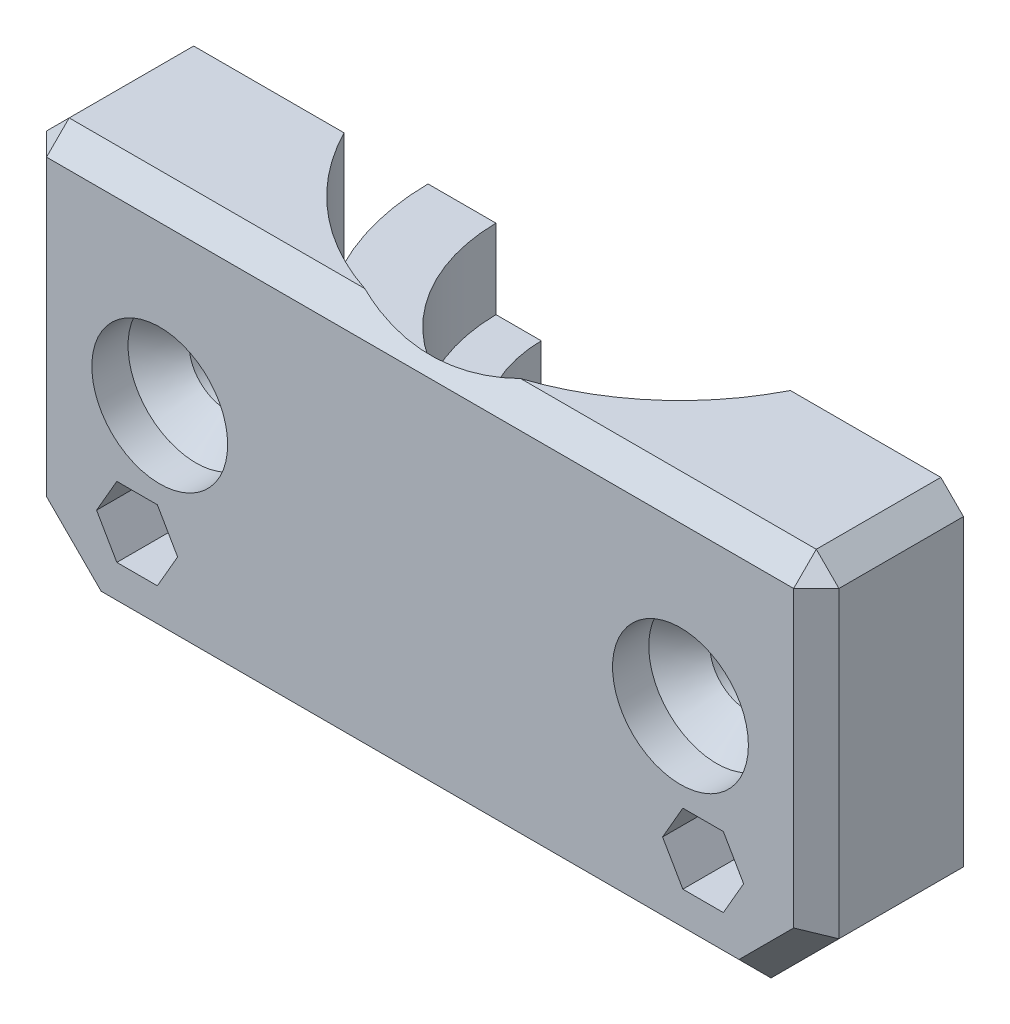
SolidWorks part; units mm, degrees
ref_plane "Front Plane" through (0, 0, 0) normal (0, 0, 1) x (1, 0, 0)
ref_plane "Top Plane" through (0, 0, 0) normal (0, 1, 0) x (1, 0, 0)
ref_plane "Right Plane" through (0, 0, 0) normal (1, 0, 0) x (0, 0, -1)
sketch "Sketch1" plane through (0, 0, 0) normal (0, 1, 0) x (1, 0, 0)
  circle A0 centre (0, 0) radius 8.05
  circle A1 centre (0, 0) radius 11.05
  dimension "D1" = 16.1
  dimension "D2" = 3
extrude "Boss-Extrude1" add sketch "Sketch1" along normal blind 3.5
sketch "Sketch2" plane through (0, 0, 0) normal (0, -1, 0) x (-1, 0, 0)
  circle A0 centre (0, 0) radius 6.05
  circle A1 centre (0, 0) radius 11.05
  dimension "D1" = 12.1
  dimension "D2" = 5
extrude "Boss-Extrude2" add sketch "Sketch2" along normal blind 5.9
sketch "Sketch3" plane through (0, -5.9, 0) normal (0, -1, 0) x (-1, 0, 0)
  circle A0 centre (0, 0) radius 8.05
  circle A1 centre (0, 0) radius 11.05
  dimension "D1" = 16.1
  dimension "D2" = 3
extrude "Boss-Extrude3" add sketch "Sketch3" along normal blind 3
sketch "Sketch5" plane through (0, 3.5, 0) normal (0, 1, 0) x (1, 0, 0)
  line L0 (9.8541, 5) -> (27, 5)
  line L1 (-27, -5) -> (-9.8541, -5)
  line L2 (-27, -5) -> (-27, 5)
  line L3 (-27, 5) -> (-9.8541, 5)
  line L4 (27, -5) -> (27, 5)
  line L5 (9.8541, -5) -> (27, -5)
  circle A0 centre (0, 0) radius 11.05 construction
  circle A1 centre (-21.75, 0) radius 1.5
  circle A2 centre (21.75, 0) radius 1.5
  circle A3 centre (0, 0) radius 2.05
  circle A4 centre (0, 0) radius 11.05
  circle M6 centre (0, 0) radius 11.05
  circle M7 centre (0, 0) radius 8.05
  dimension "D5" = 3
  dimension "D8" = 4.1
  dimension "D11" = 22.1
  dimension "D1" = 10
  dimension "D2" = 54
  dimension "D3" = 27
  dimension "D4" = 5
  dimension "D6" = 5.25
  dimension "D9" = 5
  dimension "D10" = 27
  dimension "D7" = 2
extrude "Boss-Extrude5" add sketch "Sketch5" along normal blind 5 contours L3 L2 L1 A1 M6 | M6 M7 | L5 L4 L0 A2 M6 | A3 M7 region at (18.6942, 3.5, 0) region at (10.4429, 3.5, -2.4978) region at (-18.6942, 3.5, 0) region at (-7.8223, 3.5, 0)
sketch "Sketch6" plane through (0, 8.5, 0) normal (0, 1, 0) x (1, 0, 0)
  line L0 (-27, -5) -> (-9.8541, -5) construction
  line L1 (-15.5, -5) -> (-9.8541, -5)
  line L2 (-15.5, -5) -> (-15.5, -15)
  line L3 (-15.5, -15) -> (15.5, -15)
  line L4 (15.5, -5) -> (15.5, -15)
  line L5 (9.8541, -5) -> (15.5, -5)
  circle A0 centre (0, 0) radius 2.05 construction
  arc A1 (-9.8541, -5) -> (9.8541, -5) centre (0, 0) ccw
  point P6 (0, -15)
  dimension "D4" = 11.05
  dimension "D1" = 31
  dimension "D3" = 10
extrude "Boss-Extrude6" add sketch "Sketch6" against normal blind 22.5
sketch "Sketch8" plane through (0, -14, 0) normal (0, -1, 0) x (-1, 0, 0)
  line L0 (15.5, -15) -> (-15.5, -15) construction
  line L1 (-8, -15) -> (8, -15)
  line L2 (-8, -15) -> (-8, -5)
  line L3 (-8, -5) -> (8, -5)
  line L4 (8, -15) -> (8, -5)
  circle A0 centre (0, 0) radius 12
  point P6 (0, -15)
  line M6 (15.5, -5) -> (9.8541, -5)
  arc M7 (9.8541, -5) -> (-9.8541, -5) centre (0, 0) cw
  line M8 (-9.8541, -5) -> (-15.5, -5)
  line M10 (-15.5, -15) -> (15.5, -15)
  dimension "D4" = 24
  dimension "D1" = 10
  dimension "D2" = 16
  dimension "D3" = 0
extrude "Cut-Extrude2" cut sketch "Sketch8" against normal blind 5.1 contours A0 L2 L4 M10 | L2 A0 L4 M7 | L4 L3 L2 M7 | A0 L2 M8 M7 | L4 A0 M6 M7 region at (0, -14, 12.9198) region at (9.3108, -14, 6.7422) region at (7.8341, -14, 8.2834) region at (-9.3108, -14, 6.7422) region at (0, -14, 7.5931)
ref_plane "Plane1" through (0, 0, 0.1) normal (0, 0, 1) x (1, 0, 0)
sketch "Sketch11" plane through (0, 0, 0.1) normal (0, 0, 1) x (1, 0, 0)
  line L0 (9.8541, 3.5) -> (27, 3.5) construction
  line L1 (33.7519, -27.3661) -> (-35.342, -27.3661)
  line L2 (33.7519, -27.3661) -> (33.7519, 3.5)
  line L3 (33.7519, 3.5) -> (-35.342, 3.5)
  line L4 (-35.342, -27.3661) -> (-35.342, 3.5)
  dimension "D1" = 0
extrude "Cut-Extrude4" cut sketch "Sketch11" against normal through all
sketch "Sketch13" plane through (0, 8.5, 0) normal (0, 1, 0) x (1, 0, 0)
  line L0 (27, -5) -> (27, 5) construction
  line L1 (-27, 5) -> (27, 5)
  line L2 (-27, 5) -> (-27, -5)
  line L3 (-27, -5) -> (27, -5)
  line L4 (27, 5) -> (27, -5)
  line L5 (15.5, -5) -> (27, -5) construction
  circle A0 centre (0, 0) radius 11.05
  line M1 (-27, -5) -> (-15.5, -5)
  line M5 (15.5, -5) -> (27, -5)
  line M6 (27, -5) -> (27, 5)
  line M7 (27, 5) -> (9.8541, 5)
  arc M8 (9.8541, 5) -> (-9.8541, 5) centre (0, 0) ccw
  line M9 (-9.8541, 5) -> (-27, 5)
  line M10 (-27, 5) -> (-27, -5)
  circle M11 centre (-21.75, 0) radius 1.5
  circle M12 centre (21.75, 0) radius 1.5
  circle M13 centre (0, 0) radius 2.05
  dimension "D1" = 22.1
extrude "Cut-Extrude6" cut sketch "Sketch13" against normal blind 5 contours A0 L3 M9 M10 M1 M11 | A0 L3 M5 M6 M7 M12 | L3 A0 | L3 A0 L1 M13 | L1 M8 region at (-18.6942, 8.5, 0) region at (0, 8.5, -7.4876) region at (0, 8.5, -4.7574) region at (18.6942, 8.5, 0) region at (0, 8.5, 7.4876)
sketch "Sketch14" plane through (0, 0, 15) normal (0, 0, 1) x (1, 0, 0)
  line L0 (15.5, -14) -> (15.5, 8.5) construction
  line L1 (-15.5, -14) -> (-15.5, 8.5) construction
  line L2 (-15.5, 8.5) -> (15.5, 8.5) construction
  circle A0 centre (11.5, 0.5) radius 1.65
  circle A1 centre (-11.5, 0.5) radius 1.65
  dimension "D1" = 3.3
  dimension "D2" = 3.3
  dimension "D3" = 4
  dimension "D4" = 4
  dimension "D5" = 8
  dimension "D6" = 8
extrude "Cut-Extrude7" cut sketch "Sketch14" against normal through all
sketch "草图1" plane through (0, 0, 15) normal (0, 0, 1) x (1, 0, 0)
  line L1 (-15.5, 8.5) -> (15.5, 8.5)
  line L2 (-15.5, 8.5) -> (-15.5, -14)
  line L3 (-15.5, -14) -> (15.5, -14)
  line L4 (15.5, 8.5) -> (15.5, -14)
extrude "切除-拉伸1" cut sketch "草图1" against normal blind 3.5
sketch "草图3" plane through (0, 0, 11.5) normal (0, 0, 1) x (1, 0, 0)
  circle A0 centre (-11.5, 0.5) radius 3
  circle A1 centre (11.5, 0.5) radius 3
  dimension "D1" = 6
  dimension "D2" = 6
extrude "切除-拉伸3" cut sketch "草图3" against normal blind 1.6
chamfer "倒角2" distance 1.35 angle 45 2 edges at (13.15, 0.5, 9.9) (-9.85, 0.5, 9.9)
sketch "草图4" plane through (0, 0, 11.5) normal (0, 0, 1) x (1, 0, 0)
  line L0 (-15.5, 8.5) -> (-15.5, -14) construction
  line L1 (15.5, -14) -> (15.5, 8.5) construction
  line L2 (8, -8.9) -> (-8, -8.9) construction
  circle A0 centre (-12.5, -4.9) radius 1.55
  circle A1 centre (12.5, -4.9) radius 1.55
  dimension "D1" = 3.1
  dimension "D2" = 3.1
  dimension "D3" = 3
  dimension "D4" = 3
  dimension "D5" = 4
  dimension "D6" = 4
extrude "切除-拉伸4" cut sketch "草图4" against normal through all
sketch "草图9" plane through (0, 0, 5) normal (0, 0, -1) x (-1, 0, 0)
  circle A0 centre (-12.5, -4.9) radius 1.8
  circle A1 centre (12.5, -4.9) radius 1.8
  dimension "D1" = 3.6
  dimension "D2" = 3.6
extrude "切除-拉伸6" cut sketch "草图9" against normal blind 1
sketch "草图10" plane through (0, 0, 6) normal (0, 0, -1) x (-1, 0, 0)
  line L1 (-10.7102, -4.9) -> (-11.6051, -3.35)
  line L2 (-11.6051, -3.35) -> (-13.3949, -3.35)
  line L3 (-13.3949, -3.35) -> (-14.2898, -4.9)
  line L4 (-14.2898, -4.9) -> (-13.3949, -6.45)
  line L5 (-13.3949, -6.45) -> (-11.6051, -6.45)
  line L6 (-11.6051, -6.45) -> (-10.7102, -4.9)
  line L7 (14.2898, -4.9) -> (13.3949, -3.35)
  line L8 (13.3949, -3.35) -> (11.6051, -3.35)
  line L9 (11.6051, -3.35) -> (10.7102, -4.9)
  line L10 (10.7102, -4.9) -> (11.6051, -6.45)
  line L11 (11.6051, -6.45) -> (13.3949, -6.45)
  line L12 (13.3949, -6.45) -> (14.2898, -4.9)
  circle A0 centre (-12.5, -4.9) radius 1.55 construction
  circle A1 centre (12.5, -4.9) radius 1.55 construction
  dimension "D1" = 3.1
  dimension "D2" = 3.1
extrude "切除-拉伸7" cut sketch "草图10" against normal through all
fillet "圆角1" radius 0.5 2 edges at (-14.3, -4.9, 5) (10.7, -4.9, 5)
chamfer "倒角5" distance 0.25 angle 45 12 edges at (-12.5, -3.35, 6) (-11.1577, -4.125, 6) (-11.1577, -5.675, 6) (-12.5, -6.45, 6) (-13.8423, -5.675, 6) (-13.8423, -4.125, 6) (11.1577, -4.125, 6) (11.1577, -5.675, 6) (12.5, -6.45, 6) (13.8423, -5.675, 6) (13.8423, -4.125, 6) (12.5, -3.35, 6)
sketch "草图5" plane through (15.5, 0, 0) normal (1, 0, 0) x (0, 0, -1)
  line L1 (-11.5, 8.5) -> (-5, 8.5)
  line L2 (-11.5, 8.5) -> (-11.5, -14)
  line L3 (-11.5, -14) -> (-5, -14)
  line L4 (-5, 8.5) -> (-5, -14)
extrude "凸台-拉伸1" add sketch "草图5" along normal blind 2
sketch "草图7" plane through (-15.5, 0, 0) normal (-1, 0, 0) x (0, 0, 1)
  line L1 (11.5, -14) -> (5, -14)
  line L2 (11.5, -14) -> (11.5, 8.5)
  line L3 (11.5, 8.5) -> (5, 8.5)
  line L4 (5, -14) -> (5, 8.5)
extrude "凸台-拉伸2" add sketch "草图7" along normal blind 2
sketch "草图8" plane through (0, 0, 11.5) normal (0, 0, 1) x (1, 0, 0)
  line L0 (17.5, 8.5) -> (17.5, -14) construction
  line L1 (-17.5, -14) -> (17.5, -14)
  line L2 (-17.5, -14) -> (-17.5, -8.9)
  line L3 (-17.5, -8.9) -> (17.5, -8.9)
  line L4 (17.5, -14) -> (17.5, -8.9)
  line L5 (8, -8.9) -> (-8, -8.9) construction
  dimension "D1" = 0
extrude "切除-拉伸5" cut sketch "草图8" against normal through all
chamfer "倒角3" distance 3 angle 45 2 edges at (17.5, -8.9, 8.25) (-17.5, -8.9, 8.25)
chamfer "倒角4" distance 1 angle 45 8 edges at (17.5, 1.3, 11.5) (16, -7.4, 11.5) (0, -8.9, 11.5) (-16, -7.4, 11.5) (-17.5, 1.3, 11.5) (0, 8.5, 11.5) (17.5, 8.5, 8.25) (-17.5, 8.5, 8.25)
equation "\"D3@Sketch5\"=\"D2@Sketch5\"/2"
equation "\"D4@Sketch5\"=\"D1@Sketch5\"/2"
equation "\"D6@Sketch5\"=\"D2@Sketch5\"/2-43.5/2"
equation "\"D9@Sketch5\"=\"D4@Sketch5\""
equation "\"D10@Sketch5\"=\"D3@Sketch5\""
equation "\"D1@Sketch6\"=30+1"
